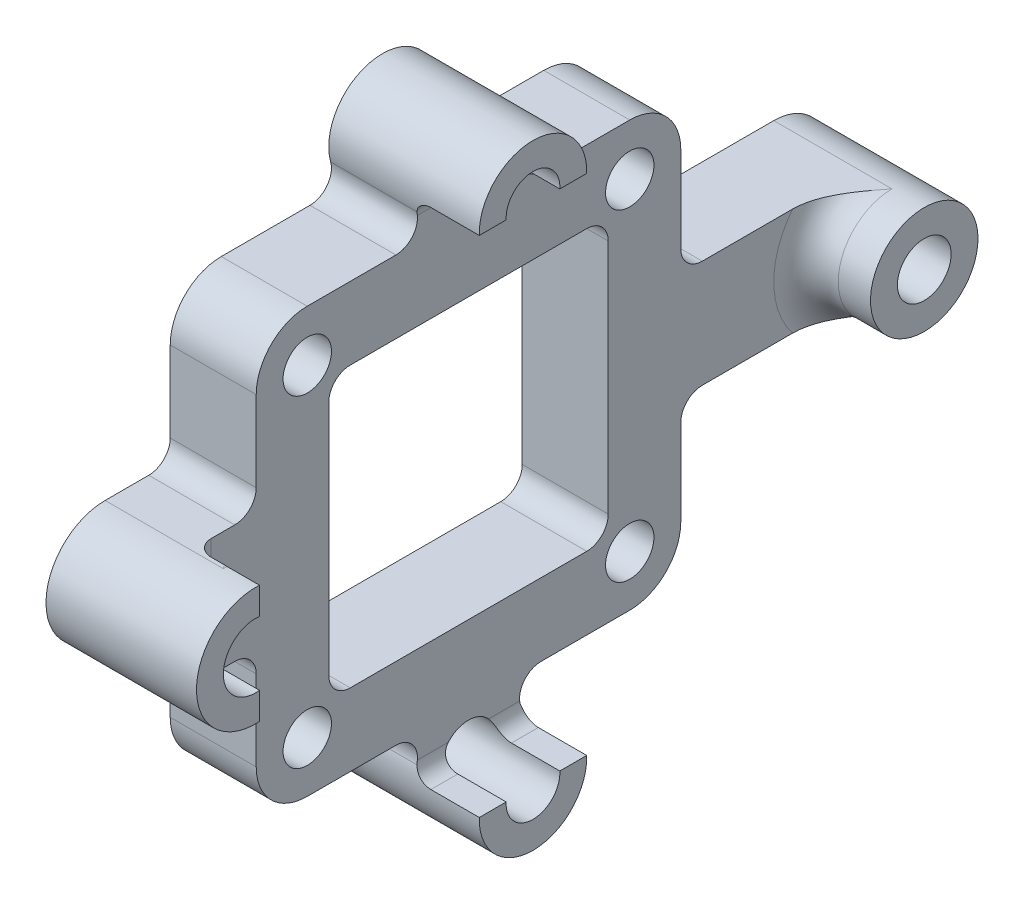
SolidWorks part; units mm, degrees
material "Beryllium S-65C, Vacuum Hot Pressed"
ref_plane "Front Plane" through (0, 0, 0) normal (1, 0, 0) x (0, 1, 0)
ref_plane "Top Plane" through (0, 0, 0) normal (0, 0, 1) x (0, 1, 0)
ref_plane "Right Plane" through (0, 0, 0) normal (0, 1, 0) x (-1, 0, 0)
sketch "Sketch1" plane through (0, 0, 0) normal (1, 0, 0) x (0, 1, 0)
sketch "Model" plane through (0, 0, 0) normal (1, 0, 0) x (0, 1, 0)
  line L0 (7, -36.4) -> (7, -53.9815)
  line L1 (-7, -36.4) -> (-7, -53.9815)
  line L2 (-7, -53.9815) -> (7, -53.9815)
  line L3 (7, -53.9815) -> (36.1014, -41.334)
  line L4 (0, 0) -> (0, -59.9211) construction
  line L5 (-7, -53.9815) -> (-36.1014, -41.334)
  line L6 (-15.7213, -20.9539) -> (-36.1014, -41.334)
  line L7 (-15.7213, -20.9539) -> (-7, -36.4)
  line L8 (15.7213, -20.9539) -> (7, -36.4)
  line L9 (36.1014, -41.334) -> (15.7213, -20.9539)
  line L10 (9.3322, 8.6384) -> (11.3322, 8.6384)
  line L11 (5.3322, 14.6384) -> (5.3322, 12.6384)
  line L12 (-5.3322, 14.6384) -> (-5.3322, 12.6384)
  line L13 (-11.3322, 8.6384) -> (-9.3322, 8.6384)
  line L14 (9.3322, -11.4697) -> (11.3322, -11.4697)
  line L15 (8.703, -13.6232) -> (10.3884, -14.7)
  line L16 (-5.3322, 14.6384) -> (5.3322, 14.6384)
  line L17 (5.3322, 12.6384) -> (-5.3322, 12.6384)
  line L18 (9.3322, -11.4697) -> (9.3322, 8.6384)
  line L19 (11.3322, 8.6384) -> (11.3322, -11.4697)
  line L20 (-5.0562, -23.046) -> (-10.3884, -14.7)
  line L21 (-10.3884, -14.7) -> (-8.703, -13.6232)
  line L22 (-8.703, -13.6232) -> (-3.3708, -21.9692)
  line L23 (-3.3708, -21.9692) -> (-5.0562, -23.046)
  line L24 (3.3708, -21.9692) -> (8.703, -13.6232)
  line L25 (10.3884, -14.7) -> (5.0562, -23.046)
  line L26 (3.3708, -21.9692) -> (5.0562, -23.046)
  line L27 (-11.3322, -11.4697) -> (-11.3322, 8.6384)
  line L28 (-9.3322, 8.6384) -> (-9.3322, -11.4697)
  line L29 (-11.3322, -11.4697) -> (-9.3322, -11.4697)
  line L30 (-7.1532, 23.5517) -> (-11.8182, 18.8569)
  line L31 (7, -36.4) -> (16.3675, -19.8094)
  line L32 (19.8245, -13.6868) -> (23.6, -7)
  line L33 (-23.6, -7) -> (-19.8245, -13.6868)
  line L34 (11.8182, 18.8569) -> (7.1532, 23.5517)
  line L35 (23.6, 7) -> (18.8366, 11.7937)
  line L36 (-16.3675, -19.8094) -> (-7, -36.4)
  line L37 (-18.8366, 11.7937) -> (-23.6, 7)
  line L38 (42.1215, -47.354) -> (36.1014, -41.334)
  line L39 (36.1014, -41.334) -> (9.7972, -52.7658)
  line L40 (7, -50.9316) -> (7, -36.4)
  line L41 (26.4236, -41.1785) -> (13.7972, -46.666)
  line L42 (18.4772, -29.3667) -> (27.0406, -37.93)
  line L43 (11.2584, -36.9935) -> (15.3215, -29.7976)
  line L44 (11, -44.8317) -> (11, -37.9769)
  line L45 (23.4176, -18.185) -> (47.354, -42.1215)
  line L46 (-36.1014, -41.334) -> (-42.1215, -47.354)
  line L47 (-7, -50.9316) -> (-7, -36.4)
  line L48 (-36.1014, -41.334) -> (-9.7972, -52.7658)
  line L49 (-11, -37.9769) -> (-11, -44.8317)
  line L50 (-15.3215, -29.7976) -> (-11.2584, -36.9935)
  line L51 (-27.0406, -37.93) -> (-18.4772, -29.3667)
  line L52 (-13.7972, -46.666) -> (-26.4236, -41.1785)
  line L53 (-47.354, -42.1215) -> (-23.4176, -18.185)
  line L54 (-23.4176, 18.185) -> (-47.354, 42.1215)
  line L55 (-42.1215, 47.354) -> (-18.185, 23.4176)
  line L56 (18.185, 23.4176) -> (42.1215, 47.354)
  line L57 (47.354, 42.1215) -> (23.4176, 18.185)
  line L58 (-26.9652, 35.0583) -> (-27.1076, 34.9484)
  line L59 (-32.6677, 40.7516) -> (-32.7868, 40.6559)
  line L60 (32.7803, 40.6611) -> (32.6631, 40.7553)
  line L61 (27.1112, 34.9456) -> (26.9658, 35.0579)
  line L62 (-33.8602, 41.9421) -> (-32.6677, 40.7516)
  line L63 (32.6631, 40.7553) -> (33.8545, 41.9467)
  arc A0 (-7, -36.4) -> (7, -36.4) centre (0, -36.4) ccw
  circle A1 centre (-15, -15) radius 2.25
  circle A2 centre (23.6, 0) radius 3
  circle A3 centre (0, -36.4) radius 3
  circle A4 centre (-15, 15) radius 2.25
  circle A5 centre (0, 25.8061) radius 3.5
  circle A6 centre (15, -15) radius 2.25
  circle A7 centre (15, 15) radius 2.25
  circle A8 centre (-23.6, 0) radius 3
  circle A9 centre (49.4975, -49.4975) radius 3
  circle A10 centre (53.9975, -49.4975) radius 1.25
  circle A11 centre (49.4975, -44.9975) radius 1.25
  circle A12 centre (49.4975, -53.9975) radius 1.25
  circle A13 centre (44.9975, -49.4975) radius 1.25
  circle A14 centre (-49.4975, -49.4975) radius 3
  circle A15 centre (-44.9975, -49.4975) radius 1.25
  circle A16 centre (-53.9975, -49.4975) radius 1.25
  circle A17 centre (-49.4975, -44.9975) radius 1.25
  circle A18 centre (-49.4975, -53.9975) radius 1.25
  circle A19 centre (-49.4975, 49.4975) radius 3
  circle A20 centre (-53.9975, 49.4975) radius 1.25
  circle A21 centre (-49.4975, 44.9975) radius 1.25
  circle A22 centre (-49.4975, 53.9975) radius 1.25
  circle A23 centre (-44.9975, 49.4975) radius 1.25
  circle A24 centre (49.4975, 49.4975) radius 3
  circle A25 centre (49.4975, 53.9975) radius 1.25
  circle A26 centre (44.9975, 49.4975) radius 1.25
  circle A27 centre (53.9975, 49.4975) radius 1.25
  circle A28 centre (49.4975, 44.9975) radius 1.25
  arc A29 (-11.8182, 18.8569) -> (-18.8366, 11.7937) centre (-15, 15) ccw
  arc A30 (-18.185, 23.4176) -> (-23.4176, 18.185) centre (-15, 15) ccw
  arc A31 (-19.8245, -13.6868) -> (-16.3675, -19.8094) centre (-15, -15) ccw
  arc A32 (-23.4176, -18.185) -> (-18.185, -23.4176) centre (-15, -15) ccw
  arc A33 (18.8366, 11.7937) -> (11.8182, 18.8569) centre (15, 15) ccw
  arc A34 (23.4176, 18.185) -> (18.185, 23.4176) centre (15, 15) ccw
  arc A35 (16.3675, -19.8094) -> (19.8245, -13.6868) centre (15, -15) ccw
  arc A36 (18.185, -23.4176) -> (23.4176, -18.185) centre (15, -15) ccw
  arc A37 (11.3322, 8.6384) -> (5.3322, 14.6384) centre (5.3322, 8.6384) ccw
  arc A38 (9.3322, 8.6384) -> (5.3322, 12.6384) centre (5.3322, 8.6384) ccw
  arc A39 (-5.3322, 14.6384) -> (-11.3322, 8.6384) centre (-5.3322, 8.6384) ccw
  arc A40 (-5.3322, 12.6384) -> (-9.3322, 8.6384) centre (-5.3322, 8.6384) ccw
  arc A41 (8.703, -13.6232) -> (9.3322, -11.4697) centre (5.3322, -11.4697) ccw
  arc A42 (10.3884, -14.7) -> (11.3322, -11.4697) centre (5.3322, -11.4697) ccw
  arc A43 (-3.3708, -21.9692) -> (3.3708, -21.9692) centre (0, -19.8157) ccw
  arc A44 (-5.0562, -23.046) -> (5.0562, -23.046) centre (0, -19.8157) ccw
  arc A45 (-11.3322, -11.4697) -> (-10.3884, -14.7) centre (-5.3322, -11.4697) ccw
  arc A46 (7.1532, 23.5517) -> (-7.1532, 23.5517) centre (0, 25.8061) ccw
  arc A47 (23.6, -7) -> (23.6, 7) centre (23.6, 0) ccw
  arc A48 (-23.6, 7) -> (-23.6, -7) centre (-23.6, 0) ccw
  arc A49 (-7, -36.4) -> (7, -36.4) centre (0, -36.4) ccw
  arc A50 (-9.3322, -11.4697) -> (-8.703, -13.6232) centre (-5.3322, -11.4697) ccw
  arc A51 (52.4421, -44.2698) -> (47.777, -42.4994) centre (49.4975, -44.9975) ccw
  arc A52 (54.5148, -46.2072) -> (52.4421, -44.2698) centre (49.4975, -49.4975) ccw
  arc A53 (54.5148, -52.7878) -> (54.5148, -46.2072) centre (53.9975, -49.4975) ccw
  arc A54 (52.4421, -54.7252) -> (54.5148, -52.7878) centre (49.4975, -49.4975) ccw
  arc A55 (46.5528, -54.7252) -> (52.4421, -54.7252) centre (49.4975, -53.9975) ccw
  arc A56 (44.4801, -52.7878) -> (46.5528, -54.7252) centre (49.4975, -49.4975) ccw
  arc A57 (42.3007, -47.5427) -> (44.4801, -52.7878) centre (44.9975, -49.4975) ccw
  arc A58 (7, -50.9316) -> (9.7972, -52.7658) centre (9, -50.9316) ccw
  arc A59 (11, -44.8317) -> (13.7972, -46.666) centre (13, -44.8317) ccw
  arc A60 (26.4236, -41.1785) -> (27.0406, -37.93) centre (25.6264, -39.3443) ccw
  arc A61 (18.4772, -29.3667) -> (15.3215, -29.7976) centre (17.063, -30.7809) ccw
  arc A62 (11.2584, -36.9935) -> (11, -37.9769) centre (13, -37.9769) ccw
  arc A63 (-44.2698, -52.4421) -> (-42.4994, -47.777) centre (-44.9975, -49.4975) ccw
  arc A64 (-46.2072, -54.5148) -> (-44.2698, -52.4421) centre (-49.4975, -49.4975) ccw
  arc A65 (-52.7878, -54.5148) -> (-46.2072, -54.5148) centre (-49.4975, -53.9975) ccw
  arc A66 (-54.7252, -52.4421) -> (-52.7878, -54.5148) centre (-49.4975, -49.4975) ccw
  arc A67 (-54.7252, -46.5528) -> (-54.7252, -52.4421) centre (-53.9975, -49.4975) ccw
  arc A68 (-52.7878, -44.4801) -> (-54.7252, -46.5528) centre (-49.4975, -49.4975) ccw
  arc A69 (-9.7972, -52.7658) -> (-7, -50.9316) centre (-9, -50.9316) ccw
  arc A70 (-13.7972, -46.666) -> (-11, -44.8317) centre (-13, -44.8317) ccw
  arc A71 (-11, -37.9769) -> (-11.2584, -36.9935) centre (-13, -37.9769) ccw
  arc A72 (-15.3215, -29.7976) -> (-18.4772, -29.3667) centre (-17.063, -30.7809) ccw
  arc A73 (-27.0406, -37.93) -> (-26.4236, -41.1785) centre (-25.6264, -39.3443) ccw
  arc A74 (-47.5427, -42.3007) -> (-52.7878, -44.4801) centre (-49.4975, -44.9975) ccw
  arc A75 (-52.4421, 44.2698) -> (-47.777, 42.4994) centre (-49.4975, 44.9975) ccw
  arc A76 (-54.5148, 46.2072) -> (-52.4421, 44.2698) centre (-49.4975, 49.4975) ccw
  arc A77 (-54.5148, 52.7878) -> (-54.5148, 46.2072) centre (-53.9975, 49.4975) ccw
  arc A78 (-52.4421, 54.7252) -> (-54.5148, 52.7878) centre (-49.4975, 49.4975) ccw
  arc A79 (-46.5528, 54.7252) -> (-52.4421, 54.7252) centre (-49.4975, 53.9975) ccw
  arc A80 (-44.4801, 52.7878) -> (-46.5528, 54.7252) centre (-49.4975, 49.4975) ccw
  arc A81 (-42.3007, 47.5427) -> (-44.4801, 52.7878) centre (-44.9975, 49.4975) ccw
  arc A82 (44.2698, 52.4421) -> (42.4994, 47.777) centre (44.9975, 49.4975) ccw
  arc A83 (46.2072, 54.5148) -> (44.2698, 52.4421) centre (49.4975, 49.4975) ccw
  arc A84 (52.7878, 54.5148) -> (46.2072, 54.5148) centre (49.4975, 53.9975) ccw
  arc A85 (54.7252, 52.4421) -> (52.7878, 54.5148) centre (49.4975, 49.4975) ccw
  arc A86 (54.7252, 46.5528) -> (54.7252, 52.4421) centre (53.9975, 49.4975) ccw
  arc A87 (52.7878, 44.4801) -> (54.7252, 46.5528) centre (49.4975, 49.4975) ccw
  arc A88 (47.5427, 42.3007) -> (52.7878, 44.4801) centre (49.4975, 44.9975) ccw
  arc A89 (35.2957, 40.7414) -> (-35.3032, 40.7349) centre (0, 0) ccw
  arc A90 (28.3951, 36.4807) -> (-28.3922, 36.483) centre (0, 0) ccw
  arc A91 (26.9658, 35.0579) -> (-26.9652, 35.0583) centre (0, 0) ccw
  arc A92 (32.432, 40.5241) -> (-32.4363, 40.5206) centre (0, 0) ccw
  spline S0 degree 2 poles (-19.9943, 14.7617) (-20.0274, 14.7948) (-20.0882, 14.8556) knots 0 0 0 0.125 0.125 0.125
  spline S1 degree 3 poles (-20.0882, 14.8556) (-20.1186, 14.886) (-20.1563, 14.9237) (-20.1994, 14.9668) knots 0.125 0.125 0.125 0.125 0.1875 0.1875 0.1875 0.1875
  spline S2 degree 3 poles (-20.1994, 14.9668) (-20.2425, 15.0099) (-20.291, 15.0584) (-20.3442, 15.1116) knots 0.1875 0.1875 0.1875 0.1875 0.25 0.25 0.25 0.25
  spline S3 degree 3 poles (-20.3442, 15.1116) (-20.4505, 15.2179) (-20.5767, 15.3441) (-20.7142, 15.4816) knots 0.25 0.25 0.25 0.25 0.375 0.375 0.375 0.375
  spline S4 degree 3 poles (-20.7142, 15.4816) (-20.8516, 15.6191) (-21.0009, 15.7683) (-21.1609, 15.9283) knots 0.375 0.375 0.375 0.375 0.5 0.5 0.5 0.5
  spline S5 degree 3 poles (-21.1609, 15.9283) (-21.3208, 16.0882) (-21.4929, 16.2603) (-21.6705, 16.438) knots 0.5 0.5 0.5 0.5 0.625 0.625 0.625 0.625
  spline S6 degree 3 poles (-21.6705, 16.438) (-21.8482, 16.6156) (-22.0322, 16.7996) (-22.2228, 16.9902) knots 0.625 0.625 0.625 0.625 0.75 0.75 0.75 0.75
  spline S7 degree 3 poles (-22.2228, 16.9902) (-22.4133, 17.1807) (-22.6118, 17.3792) (-22.8116, 17.579) knots 0.75 0.75 0.75 0.75 0.875 0.875 0.875 0.875
  spline S8 degree 3 poles (-22.8116, 17.579) (-23.0113, 17.7787) (-23.2133, 17.9807) (-23.4176, 18.185) knots 0.875 0.875 0.875 0.875 1 1 1 1
  spline S9 degree 3 poles (-18.185, 23.4176) (-17.776, 23.0086) (-17.3796, 22.6122) (-16.9943, 22.2269) knots 0 0 0 0 0.25 0.25 0.25 0.25
  spline S10 degree 3 poles (-16.9943, 22.2269) (-16.6091, 21.8417) (-16.2547, 21.4873) (-15.9312, 21.1638) knots 0.25 0.25 0.25 0.25 0.5 0.5 0.5 0.5
  spline S11 degree 3 poles (-15.9312, 21.1638) (-15.7694, 21.002) (-15.6199, 20.8525) (-15.4833, 20.7159) knots 0.5 0.5 0.5 0.5 0.625 0.625 0.625 0.625
  spline S12 degree 3 poles (-15.4833, 20.7159) (-15.3468, 20.5794) (-15.223, 20.4556) (-15.1156, 20.3482) knots 0.625 0.625 0.625 0.625 0.75 0.75 0.75 0.75
  spline S13 degree 3 poles (-15.1156, 20.3482) (-15.0081, 20.2407) (-14.9194, 20.152) (-14.8577, 20.0903) knots 0.75 0.75 0.75 0.75 0.875 0.875 0.875 0.875
  spline S14 degree 2 poles (-14.8577, 20.0903) (-14.7961, 20.0287) (-14.7617, 19.9943) knots 0.875 0.875 0.875 1 1 1
  spline S15 degree 3 poles (-15.7213, -20.9539) (-15.8911, -21.1236) (-16.0717, -21.3043) (-16.4527, -21.6853) (-16.653, -21.8856) (-17.0746, -22.3072) (-17.2928, -22.5254) (-17.7332, -22.9658) (-17.9571, -23.1896) (-18.185, -23.4176) knots 0 0 0 0 0.25 0.25 0.5 0.5 0.75 0.75 1 1 1 1
  spline S16 degree 3 poles (-23.4176, -18.185) (-23.0086, -17.776) (-22.6122, -17.3796) (-22.2269, -16.9943) knots 0 0 0 0 0.25 0.25 0.25 0.25
  spline S17 degree 3 poles (-22.2269, -16.9943) (-21.8417, -16.6091) (-21.4873, -16.2547) (-21.1638, -15.9312) knots 0.25 0.25 0.25 0.25 0.5 0.5 0.5 0.5
  spline S18 degree 3 poles (-21.1638, -15.9312) (-21.002, -15.7694) (-20.8525, -15.6199) (-20.7159, -15.4833) knots 0.5 0.5 0.5 0.5 0.625 0.625 0.625 0.625
  spline S19 degree 3 poles (-20.7159, -15.4833) (-20.5794, -15.3468) (-20.4556, -15.223) (-20.3482, -15.1156) knots 0.625 0.625 0.625 0.625 0.75 0.75 0.75 0.75
  spline S20 degree 3 poles (-20.3482, -15.1156) (-20.2407, -15.0081) (-20.152, -14.9194) (-20.0903, -14.8577) knots 0.75 0.75 0.75 0.75 0.875 0.875 0.875 0.875
  spline S21 degree 2 poles (-20.0903, -14.8577) (-20.0287, -14.7961) (-19.9943, -14.7617) knots 0.875 0.875 0.875 1 1 1
  spline S22 degree 2 poles (14.7617, 19.9943) (14.7948, 20.0274) (14.8556, 20.0882) knots 0 0 0 0.125 0.125 0.125
  spline S23 degree 3 poles (14.8556, 20.0882) (14.886, 20.1186) (14.9237, 20.1563) (14.9668, 20.1994) knots 0.125 0.125 0.125 0.125 0.1875 0.1875 0.1875 0.1875
  spline S24 degree 3 poles (14.9668, 20.1994) (15.0099, 20.2425) (15.0584, 20.291) (15.1116, 20.3442) knots 0.1875 0.1875 0.1875 0.1875 0.25 0.25 0.25 0.25
  spline S25 degree 3 poles (15.1116, 20.3442) (15.2179, 20.4505) (15.3441, 20.5767) (15.4816, 20.7142) knots 0.25 0.25 0.25 0.25 0.375 0.375 0.375 0.375
  spline S26 degree 3 poles (15.4816, 20.7142) (15.6191, 20.8516) (15.7683, 21.0009) (15.9283, 21.1609) knots 0.375 0.375 0.375 0.375 0.5 0.5 0.5 0.5
  spline S27 degree 3 poles (15.9283, 21.1609) (16.0882, 21.3208) (16.2603, 21.4929) (16.438, 21.6705) knots 0.5 0.5 0.5 0.5 0.625 0.625 0.625 0.625
  spline S28 degree 3 poles (16.438, 21.6705) (16.6156, 21.8482) (16.7996, 22.0322) (16.9902, 22.2228) knots 0.625 0.625 0.625 0.625 0.75 0.75 0.75 0.75
  spline S29 degree 3 poles (16.9902, 22.2228) (17.1807, 22.4133) (17.3792, 22.6118) (17.579, 22.8116) knots 0.75 0.75 0.75 0.75 0.875 0.875 0.875 0.875
  spline S30 degree 3 poles (17.579, 22.8116) (17.7787, 23.0113) (17.9807, 23.2133) (18.185, 23.4176) knots 0.875 0.875 0.875 0.875 1 1 1 1
  spline S31 degree 3 poles (23.4176, 18.185) (23.0086, 17.776) (22.6122, 17.3796) (22.2269, 16.9943) knots 0 0 0 0 0.25 0.25 0.25 0.25
  spline S32 degree 3 poles (22.2269, 16.9943) (21.8417, 16.6091) (21.4873, 16.2547) (21.1638, 15.9312) knots 0.25 0.25 0.25 0.25 0.5 0.5 0.5 0.5
  spline S33 degree 3 poles (21.1638, 15.9312) (21.002, 15.7694) (20.8525, 15.6199) (20.7159, 15.4833) knots 0.5 0.5 0.5 0.5 0.625 0.625 0.625 0.625
  spline S34 degree 3 poles (20.7159, 15.4833) (20.5794, 15.3468) (20.4556, 15.223) (20.3482, 15.1156) knots 0.625 0.625 0.625 0.625 0.75 0.75 0.75 0.75
  spline S35 degree 3 poles (20.3482, 15.1156) (20.2407, 15.0081) (20.152, 14.9194) (20.0903, 14.8577) knots 0.75 0.75 0.75 0.75 0.875 0.875 0.875 0.875
  spline S36 degree 2 poles (20.0903, 14.8577) (20.0287, 14.7961) (19.9943, 14.7617) knots 0.875 0.875 0.875 1 1 1
  spline S37 degree 2 poles (19.9943, -14.7617) (20.0274, -14.7948) (20.0882, -14.8556) knots 0 0 0 0.125 0.125 0.125
  spline S38 degree 3 poles (20.0882, -14.8556) (20.1186, -14.886) (20.1563, -14.9237) (20.1994, -14.9668) knots 0.125 0.125 0.125 0.125 0.1875 0.1875 0.1875 0.1875
  spline S39 degree 3 poles (20.1994, -14.9668) (20.2425, -15.0099) (20.291, -15.0584) (20.3442, -15.1116) knots 0.1875 0.1875 0.1875 0.1875 0.25 0.25 0.25 0.25
  spline S40 degree 3 poles (20.3442, -15.1116) (20.4505, -15.2179) (20.5767, -15.3441) (20.7142, -15.4816) knots 0.25 0.25 0.25 0.25 0.375 0.375 0.375 0.375
  spline S41 degree 3 poles (20.7142, -15.4816) (20.8516, -15.6191) (21.0009, -15.7683) (21.1609, -15.9283) knots 0.375 0.375 0.375 0.375 0.5 0.5 0.5 0.5
  spline S42 degree 3 poles (21.1609, -15.9283) (21.3208, -16.0882) (21.4929, -16.2603) (21.6705, -16.438) knots 0.5 0.5 0.5 0.5 0.625 0.625 0.625 0.625
  spline S43 degree 3 poles (21.6705, -16.438) (21.8482, -16.6156) (22.0322, -16.7996) (22.2228, -16.9902) knots 0.625 0.625 0.625 0.625 0.75 0.75 0.75 0.75
  spline S44 degree 3 poles (22.2228, -16.9902) (22.4133, -17.1807) (22.6118, -17.3792) (22.8116, -17.579) knots 0.75 0.75 0.75 0.75 0.875 0.875 0.875 0.875
  spline S45 degree 3 poles (22.8116, -17.579) (23.0113, -17.7787) (23.2133, -17.9807) (23.4176, -18.185) knots 0.875 0.875 0.875 0.875 1 1 1 1
  spline S46 degree 3 poles (18.185, -23.4176) (17.9577, -23.1903) (17.7344, -22.967) (17.2949, -22.5275) (17.077, -22.3096) (16.6566, -21.8892) (16.456, -21.6886) (16.0735, -21.3061) (15.8905, -21.1231) (15.7213, -20.9539) knots 0 0 0 0 0.25 0.25 0.5 0.5 0.75 0.75 1 1 1 1
  spline S47 degree 3 poles (47.777, -42.4994) (47.7283, -42.4597) (47.6308, -42.3802) (47.4897, -42.2541) (47.3993, -42.1657) (47.354, -42.1215) knots 0 0 0 0 0.332053 0.665228 1 1 1 1
  spline S48 degree 3 poles (42.1215, -47.354) (42.1519, -47.3849) (42.2128, -47.4465) (42.2712, -47.5104) (42.3007, -47.5427) knots 0 0 0 0 0.500899 1 1 1 1
  spline S49 degree 3 poles (-42.4994, -47.777) (-42.4597, -47.7283) (-42.3802, -47.6308) (-42.2541, -47.4897) (-42.1657, -47.3993) (-42.1215, -47.354) knots 0 0 0 0 0.332053 0.665228 1 1 1 1
  spline S50 degree 3 poles (-47.354, -42.1215) (-47.3849, -42.1519) (-47.4465, -42.2128) (-47.5104, -42.2712) (-47.5427, -42.3007) knots 0 0 0 0 0.500899 1 1 1 1
  spline S51 degree 3 poles (-47.777, 42.4994) (-47.7283, 42.4597) (-47.6308, 42.3802) (-47.4897, 42.2541) (-47.3993, 42.1657) (-47.354, 42.1215) knots 0 0 0 0 0.332053 0.665228 1 1 1 1
  spline S52 degree 3 poles (-42.1215, 47.354) (-42.1519, 47.3849) (-42.2128, 47.4465) (-42.2712, 47.5104) (-42.3007, 47.5427) knots 0 0 0 0 0.500899 1 1 1 1
  spline S53 degree 3 poles (42.4994, 47.777) (42.4597, 47.7283) (42.3802, 47.6308) (42.2541, 47.4897) (42.1657, 47.3993) (42.1215, 47.354) knots 0 0 0 0 0.332053 0.665228 1 1 1 1
  spline S54 degree 3 poles (47.354, 42.1215) (47.3849, 42.1519) (47.4465, 42.2128) (47.5104, 42.2712) (47.5427, 42.3007) knots 0 0 0 0 0.500899 1 1 1 1
  spline S55 degree 3 poles (-28.5315, 33.7959) (-29.7895, 35.052) (-32.0792, 37.3379) (-34.3674, 39.6223) (-35.3987, 40.652) knots 0 0 0 0 0.007511 0.013676 0.013676 0.013676 0.013676
  spline S56 degree 2 poles (-35.3987, 40.652) (-35.3686, 40.6783) (-35.3032, 40.7349) knots 0 0 0 1 1 1
  spline S57 degree 3 poles (-35.3032, 40.7349) (-35.1099, 40.6224) (-34.9092, 40.5288) (-34.4904, 40.3852) (-34.2697, 40.3351) (-33.8275, 40.2977) (-33.6003, 40.3102) (-33.1695, 40.4177) (-32.9622, 40.5144) (-32.7868, 40.6559) knots 0 0 0 0 0.25 0.25 0.5 0.5 0.75 0.75 1 1 1 1
  spline S58 degree 3 poles (-32.7868, 40.6559) (-31.862, 39.7274) (-29.9689, 37.826) (-28.0759, 35.9226) (-27.1076, 34.9484) knots 0 0 0 0 0.005544 0.01135 0.01135 0.01135 0.01135
  spline S59 degree 3 poles (-27.1076, 34.9484) (-27.2253, 34.8571) (-27.339, 34.7679) (-27.449, 34.6808) knots 0 0 0 0 0.125 0.125 0.125 0.125
  spline S60 degree 3 poles (-27.449, 34.6808) (-27.5591, 34.5937) (-27.6622, 34.5112) (-27.7562, 34.4355) knots 0.125 0.125 0.125 0.125 0.25 0.25 0.25 0.25
  spline S61 degree 3 poles (-27.7562, 34.4355) (-27.8501, 34.3598) (-27.9353, 34.2905) (-28.01, 34.2293) knots 0.25 0.25 0.25 0.25 0.375 0.375 0.375 0.375
  spline S62 degree 3 poles (-28.01, 34.2293) (-28.0847, 34.1682) (-28.1508, 34.1137) (-28.208, 34.0664) knots 0.375 0.375 0.375 0.375 0.5 0.5 0.5 0.5
  spline S63 degree 3 poles (-28.208, 34.0664) (-28.3224, 33.9716) (-28.4014, 33.9054) (-28.4542, 33.861) knots 0.5 0.5 0.5 0.5 0.75 0.75 0.75 0.75
  spline S64 degree 2 poles (-28.4542, 33.861) (-28.5069, 33.8167) (-28.5315, 33.7959) knots 0.75 0.75 0.75 1 1 1
  spline S65 degree 3 poles (-32.6677, 40.7516) (-30.7679, 38.8549) (-28.8673, 36.9573) (-26.9652, 35.0583) knots 0 0 0 0 0.011355 0.011355 0.011355 0.011355
  spline S66 degree 3 poles (26.9658, 35.0579) (28.8661, 36.9582) (30.765, 38.8572) (32.6631, 40.7553) knots 0 0 0 0 0.011354 0.011354 0.011354 0.011354
  spline S67 degree 3 poles (27.1112, 34.9456) (28.0774, 35.9208) (29.9671, 37.8268) (31.8569, 39.731) (32.7803, 40.6611) knots 0 0 0 0 0.005803 0.011349 0.011349 0.011349 0.011349
  spline S68 degree 3 poles (35.3918, 40.658) (34.3627, 39.6272) (32.0785, 37.3393) (29.7928, 35.0499) (28.5366, 33.7916) knots 0 0 0 0 0.006163 0.013675 0.013675 0.013675 0.013675
  spline S69 degree 2 poles (28.5366, 33.7916) (28.5119, 33.8125) (28.46, 33.8561) knots 0 0 0 0.25 0.25 0.25
  spline S70 degree 3 poles (28.46, 33.8561) (28.4081, 33.8998) (28.3276, 33.9673) (28.2139, 34.0615) knots 0.25 0.25 0.25 0.25 0.5 0.5 0.5 0.5
  spline S71 degree 3 poles (28.2139, 34.0615) (28.157, 34.1086) (28.0907, 34.1633) (28.0156, 34.2247) knots 0.5 0.5 0.5 0.5 0.625 0.625 0.625 0.625
  spline S72 degree 3 poles (28.0156, 34.2247) (27.9405, 34.2862) (27.857, 34.3542) (27.7624, 34.4305) knots 0.625 0.625 0.625 0.625 0.75 0.75 0.75 0.75
  spline S73 degree 3 poles (27.7624, 34.4305) (27.6678, 34.5068) (27.5654, 34.5887) (27.4554, 34.6758) knots 0.75 0.75 0.75 0.75 0.875 0.875 0.875 0.875
  spline S74 degree 3 poles (27.4554, 34.6758) (27.3453, 34.763) (27.2291, 34.8541) (27.1112, 34.9456) knots 0.875 0.875 0.875 0.875 1 1 1 1
  spline S75 degree 3 poles (32.7803, 40.6611) (32.868, 40.5904) (32.9621, 40.5316) (33.1614, 40.435) (33.2679, 40.397) (33.5926, 40.3156) (33.8191, 40.3033) (34.2611, 40.3406) (34.4783, 40.3897) (34.901, 40.5344) (35.1025, 40.6287) (35.2957, 40.7414) knots 0 0 0 0 0.125 0.125 0.25 0.25 0.5 0.5 0.75 0.75 1 1 1 1
  spline S76 degree 2 poles (35.2957, 40.7414) (35.3615, 40.6845) (35.3918, 40.658) knots 0 0 0 1 1 1
sketch "Sketch3" plane through (0, 0, 0) normal (1, 0, 0) x (0, 1, 0)
  line L0 (-15, 19.75) -> (15, 19.75)
  line L1 (-19.75, 15) -> (-19.75, -15)
  line L2 (-15, -19.75) -> (15, -19.75)
  line L3 (19.75, 15) -> (19.75, -15)
  circle A0 centre (-15, 15) radius 2.25
  circle A1 centre (15, 15) radius 2.25
  circle A2 centre (15, -15) radius 2.25
  circle A3 centre (-15, -15) radius 2.25
  arc A4 (-15, 19.75) -> (-19.75, 15) centre (-15, 15) ccw
  arc A5 (19.75, 15) -> (15, 19.75) centre (15, 15) ccw
  arc A6 (-19.75, -15) -> (-15, -19.75) centre (-15, -15) ccw
  arc A7 (15, -19.75) -> (19.75, -15) centre (15, -15) ccw
  circle A8 centre (-15, 15) radius 4.75 construction
  circle A9 centre (15, 15) radius 4.75 construction
  circle A10 centre (15, -15) radius 4.75 construction
  circle A11 centre (-15, -15) radius 4.75 construction
  dimension "D1" = 2.5
extrude "Boss-Extrude1" add sketch "Sketch3" along normal blind 3
sketch "Sketch4" plane through (0, 0, 0) normal (-1, 0, 0) x (0, -1, 0)
  line L0 (-5.5, 25.8061) -> (-5.5, 19.75)
  line L1 (-15, 19.75) -> (15, 19.75) construction
  line L2 (5.5, 25.8061) -> (5.5, 19.75)
  line L3 (5, -36.4) -> (5, -19.75)
  line L5 (15, -19.75) -> (-15, -19.75) construction
  line L6 (-5, -36.4) -> (-5.2114, -19.75)
  line L7 (-5.2114, -19.75) -> (5, -19.75)
  line L8 (-5.5, 19.75) -> (5.5, 19.75)
  circle A0 centre (0, 25.8061) radius 3.5
  circle A1 centre (-23.6, 0) radius 3
  circle A2 centre (0, -36.4) radius 3
  circle A3 centre (23.6, 0) radius 3
  circle A4 centre (0, 25.8061) radius 5.5
  circle A5 centre (-23.6, 0) radius 5
  circle A6 centre (23.6, 0) radius 5
  circle A7 centre (0, -36.4) radius 5
  line M9 (15, 19.75) -> (-15, 19.75)
  line M11 (-19.75, 15) -> (-19.75, -15)
  line M15 (19.75, -15) -> (19.75, 15)
  dimension "D1" = 2
extrude "Boss-Extrude2" add sketch "Sketch4" against normal up to surface (3 mm away) contours A6 A3 M15 | A4 A0 | A4 L0 L2 M9 | A5 A1 M11 | A7 A2 region at (0, 0, 20.1806) region at (0, 0, 31.1506) region at (0, 0, -41.2586) region at (0, 19.8835, 0) region at (0, -25.2503, -4.5781) up to face at (3, 15, -17.25)
sketch "Sketch5" plane through (3, 0, 0) normal (1, 0, 0) x (0, 1, 0)
  line L9 (-5, -36.4) -> (-5, -19.75)
  line L10 (5, -36.4) -> (5, -19.75)
  line L11 (-5, -19.75) -> (5, -19.75)
  circle A7 centre (0, -36.4) radius 5 construction
  circle A9 centre (0, -36.4) radius 5
  arc A10 (5, -36.4) -> (-5, -36.4) centre (0, -36.4) ccw
  dimension "D1" = 0
extrude "Boss-Extrude3" add sketch "Sketch5" against normal up to surface (3 mm away) up to face at (0, 0, 6.0383)
sketch "Sketch6" plane through (3, 0, 0) normal (1, 0, 0) x (0, 1, 0)
  line L4 (-13, -13) -> (-13, 13)
  line L5 (-13, 13) -> (13, 13)
  line L6 (13, 13) -> (13, -13)
  line L7 (13, -13) -> (-13, -13)
extrude "Cut-Extrude1" cut sketch "Sketch6" against normal blind 6
fillet "Fillet1" radius 2 8 edges at (1.5, 19.75, 3.1902) (1.5, 19.75, -3.1902) (1.5, -19.75, 3.1902) (1.5, -19.75, -3.1902) (1.5, -5, -19.75) (1.5, 5, -19.75) (1.5, -5.5, 19.75) (1.5, 5.5, 19.75)
fillet "Fillet2" radius 2 4 edges at (1.5, 13, -13) (1.5, -13, -13) (1.5, -13, 13) (1.5, 13, 13)
sketch "Sketch7" plane through (3, 0, 0) normal (1, 0, 0) x (0, 1, 0)
  circle A0 centre (0, 25.8061) radius 5.5
  circle A1 centre (23.6, 0) radius 5
  circle A2 centre (-23.6, 0) radius 5
  circle A3 centre (0, -36.4) radius 5
  circle A4 centre (-23.6, 0) radius 3
  circle A5 centre (0, 25.8061) radius 3.5
  circle A6 centre (23.6, 0) radius 3
  circle A7 centre (0, -36.4) radius 3
extrude "Boss-Extrude4" add sketch "Sketch7" along normal blind 6
fillet "Fillet3" radius 3 4 edges at (3, 18.6, 0) (3, 0, -31.4) (3, -18.6, 0) (3, 0, 20.3061)
sketch "Sketch8" plane through (9, 0, 0) normal (1, 0, 0) x (0, 1, 0)
  circle A0 centre (0, -36.4) radius 3 construction
  circle A1 centre (-23.6, 0) radius 3 construction
  circle A2 centre (0, 25.8061) radius 3.5 construction
  circle A3 centre (23.6, 0) radius 3 construction
  circle A4 centre (0, -36.4) radius 3
  circle A5 centre (-23.6, 0) radius 3
  circle A6 centre (0, 25.8061) radius 3.5
  circle A7 centre (23.6, 0) radius 3
  circle A8 centre (0, -36.4) radius 2.5
  circle A9 centre (-23.6, 0) radius 2.5
  circle A10 centre (0, 25.8061) radius 3
  circle A11 centre (23.6, 0) radius 2.5
  dimension "D1" = 0.5
extrude "Boss-Extrude5" add sketch "Sketch8" against normal up to surface (9 mm away) up to face at (0, 0, 0)
sketch "Sketch9" plane through (3, 0, 0) normal (1, 0, 0) x (0, 1, 0)
  line L1 (-23.4462, 25.4449) -> (23.4462, 25.4449)
  line L2 (-23.4462, 25.4449) -> (-23.4462, -25.4449)
  line L3 (-23.4462, -25.4449) -> (23.4462, -25.4449)
  line L4 (23.4462, 25.4449) -> (23.4462, -25.4449)
  line L5 (-23.4462, 25.4449) -> (23.4462, -25.4449) construction
  line L6 (-23.4462, -25.4449) -> (23.4462, 25.4449) construction
  point P0 (0, 0)
sketch "Sketch10" plane through (9, 0, 0) normal (1, 0, 0) x (0, 1, 0)
  line L0 (-23.4462, -25.4449) -> (23.4462, -25.4449) construction
  line L1 (-23.4462, 25.4449) -> (-23.4462, -25.4449) construction
  line L2 (-23.4462, 25.4449) -> (23.4462, 25.4449) construction
  line L3 (23.4462, 25.4449) -> (23.4462, -25.4449) construction
  line L4 (-23.4462, -25.4449) -> (23.4462, -25.4449)
  line L5 (-23.4462, 25.4449) -> (-23.4462, -25.4449)
  line L6 (-23.4462, 25.4449) -> (23.4462, 25.4449)
  line L7 (23.4462, 25.4449) -> (23.4462, -25.4449)
extrude "Cut-Extrude2" cut sketch "Sketch10" against normal up to surface (6 mm away) up to face at (3, 0, -2.908)
fillet "Fillet4" radius 1.5 6 edges at (3, 23.4462, -3.7464) (3, 23.4462, 3.7464) (3, 4.2391, 25.4449) (3, -4.2391, 25.4449) (3, -23.4462, -3.7464) (3, -23.4462, 3.7464)
sketch "Sketch11" plane through (0, 0, 0) normal (-1, 0, 0) x (0, -1, 0)
  line L12 (15, 19.75) -> (7.5, 19.75)
  line L13 (5.5, 21.75) -> (5.5, 25.8061)
  line L14 (-5.5, 25.8061) -> (-5.5, 21.75)
  line L15 (-7.5, 19.75) -> (-15, 19.75)
  line L16 (-19.75, 15) -> (-19.75, 6.7511)
  line L17 (-19.75, -6.7511) -> (-19.75, -15)
  line L18 (-15, -19.75) -> (-7, -19.75)
  line L19 (-5, -21.75) -> (-5, -36.4)
  line L20 (5, -36.4) -> (5, -21.75)
  line L21 (7, -19.75) -> (15, -19.75)
  line L22 (19.75, -15) -> (19.75, -6.7511)
  line L23 (19.75, 6.7511) -> (19.75, 15)
  line L24 (15, 19.75) -> (7.5, 19.75)
  line L25 (5.5, 21.75) -> (5.5, 25.8061)
  line L26 (-5.5, 25.8061) -> (-5.5, 21.75)
  line L27 (-7.5, 19.75) -> (-15, 19.75)
  line L28 (-19.75, 15) -> (-19.75, 6.7511)
  line L29 (-19.75, -6.7511) -> (-19.75, -15)
  line L30 (-15, -19.75) -> (-7, -19.75)
  line L31 (-5, -21.75) -> (-5, -36.4)
  line L32 (5, -36.4) -> (5, -21.75)
  line L33 (7, -19.75) -> (15, -19.75)
  line L34 (19.75, -15) -> (19.75, -6.7511)
  line L35 (19.75, 6.7511) -> (19.75, 15)
  circle A0 centre (0, -36.4) radius 2.5 construction
  circle A1 centre (15, -15) radius 2.25 construction
  circle A2 centre (-15, -15) radius 2.25 construction
  circle A3 centre (-15, 15) radius 2.25 construction
  circle A4 centre (15, 15) radius 2.25 construction
  circle A5 centre (23.6, 0) radius 2.5 construction
  circle A6 centre (0, 25.8061) radius 3 construction
  circle A7 centre (-23.6, 0) radius 2.5 construction
  circle A8 centre (0, -36.4) radius 2.5
  circle A9 centre (15, -15) radius 2.25
  circle A10 centre (-15, -15) radius 2.25
  circle A11 centre (-15, 15) radius 2.25
  circle A12 centre (15, 15) radius 2.25
  circle A13 centre (23.6, 0) radius 2.5
  circle A14 centre (0, 25.8061) radius 3
  circle A15 centre (-23.6, 0) radius 2.5
  arc A16 (19.75, 15) -> (15, 19.75) centre (15, 15) ccw
  arc A17 (5.5, 21.75) -> (7.5, 19.75) centre (7.5, 21.75) ccw
  arc A18 (5.5, 25.8061) -> (-5.5, 25.8061) centre (0, 25.8061) ccw
  arc A19 (-7.5, 19.75) -> (-5.5, 21.75) centre (-7.5, 21.75) ccw
  arc A20 (-15, 19.75) -> (-19.75, 15) centre (-15, 15) ccw
  arc A21 (-22.2786, 4.8222) -> (-19.75, 6.7511) centre (-21.75, 6.7511) ccw
  arc A22 (-22.2786, 4.8222) -> (-22.2786, -4.8222) centre (-23.6, 0) ccw
  arc A23 (-19.75, -6.7511) -> (-22.2786, -4.8222) centre (-21.75, -6.7511) ccw
  arc A24 (-19.75, -15) -> (-15, -19.75) centre (-15, -15) ccw
  arc A25 (-5, -21.75) -> (-7, -19.75) centre (-7, -21.75) ccw
  arc A26 (-5, -36.4) -> (5, -36.4) centre (0, -36.4) ccw
  arc A27 (7, -19.75) -> (5, -21.75) centre (7, -21.75) ccw
  arc A28 (15, -19.75) -> (19.75, -15) centre (15, -15) ccw
  arc A29 (22.2786, -4.8222) -> (19.75, -6.7511) centre (21.75, -6.7511) ccw
  arc A30 (22.2786, -4.8222) -> (22.2786, 4.8222) centre (23.6, 0) ccw
  arc A31 (19.75, 6.7511) -> (22.2786, 4.8222) centre (21.75, 6.7511) ccw
  arc A32 (19.75, 15) -> (15, 19.75) centre (15, 15) ccw
  arc A33 (5.5, 21.75) -> (7.5, 19.75) centre (7.5, 21.75) ccw
  arc A34 (5.5, 25.8061) -> (-5.5, 25.8061) centre (0, 25.8061) ccw
  arc A35 (-7.5, 19.75) -> (-5.5, 21.75) centre (-7.5, 21.75) ccw
  arc A36 (-15, 19.75) -> (-19.75, 15) centre (-15, 15) ccw
  arc A37 (-22.2786, 4.8222) -> (-19.75, 6.7511) centre (-21.75, 6.7511) ccw
  arc A38 (-22.2786, 4.8222) -> (-22.2786, -4.8222) centre (-23.6, 0) ccw
  arc A39 (-19.75, -6.7511) -> (-22.2786, -4.8222) centre (-21.75, -6.7511) ccw
  arc A40 (-19.75, -15) -> (-15, -19.75) centre (-15, -15) ccw
  arc A41 (-5, -21.75) -> (-7, -19.75) centre (-7, -21.75) ccw
  arc A42 (-5, -36.4) -> (5, -36.4) centre (0, -36.4) ccw
  arc A43 (7, -19.75) -> (5, -21.75) centre (7, -21.75) ccw
  arc A44 (15, -19.75) -> (19.75, -15) centre (15, -15) ccw
  arc A45 (22.2786, -4.8222) -> (19.75, -6.7511) centre (21.75, -6.7511) ccw
  arc A46 (22.2786, -4.8222) -> (22.2786, 4.8222) centre (23.6, 0) ccw
  arc A47 (19.75, 6.7511) -> (22.2786, 4.8222) centre (21.75, 6.7511) ccw
  dimension "D1" = 0
extrude "Boss-Extrude6" add sketch "Sketch11" along normal blind 5
sketch "Sketch13" plane through (-5, 0, 0) normal (-1, 0, 0) x (0, -1, 0)
  circle A2 centre (0, 25.8061) radius 2.5
  circle A3 centre (0, 25.8061) radius 2.5
  circle A5 centre (0, 25.8061) radius 3.5
  circle A6 centre (0, 25.8061) radius 3.5
  dimension "D1" = 0.5
  dimension "D2" = 0.5
extrude "Boss-Extrude7" add sketch "Sketch13" against normal up to surface (8 mm away) up to face at (3, 0, 1.0613)
sketch "Sketch14" plane through (0, 0, 0) normal (1, 0, 0) x (0, 1, 0)
  line L4 (-11, -13) -> (11, -13)
  line L5 (13, -11) -> (13, 11)
  line L6 (11, 13) -> (-11, 13)
  line L7 (-13, 11) -> (-13, -11)
  line L8 (-11, -13) -> (11, -13)
  line L9 (13, -11) -> (13, 11)
  line L10 (11, 13) -> (-11, 13)
  line L11 (-13, 11) -> (-13, -11)
  arc A4 (11, -13) -> (13, -11) centre (11, -11) ccw
  arc A5 (13, 11) -> (11, 13) centre (11, 11) ccw
  arc A6 (-11, 13) -> (-13, 11) centre (-11, 11) ccw
  arc A7 (-13, -11) -> (-11, -13) centre (-11, -11) ccw
  arc A8 (11, -13) -> (13, -11) centre (11, -11) ccw
  arc A9 (13, 11) -> (11, 13) centre (11, 11) ccw
  arc A10 (-11, 13) -> (-13, 11) centre (-11, 11) ccw
  arc A11 (-13, -11) -> (-11, -13) centre (-11, -11) ccw
  dimension "D1" = 0
extrude "Cut-Extrude3" cut sketch "Sketch14" against normal blind 54
